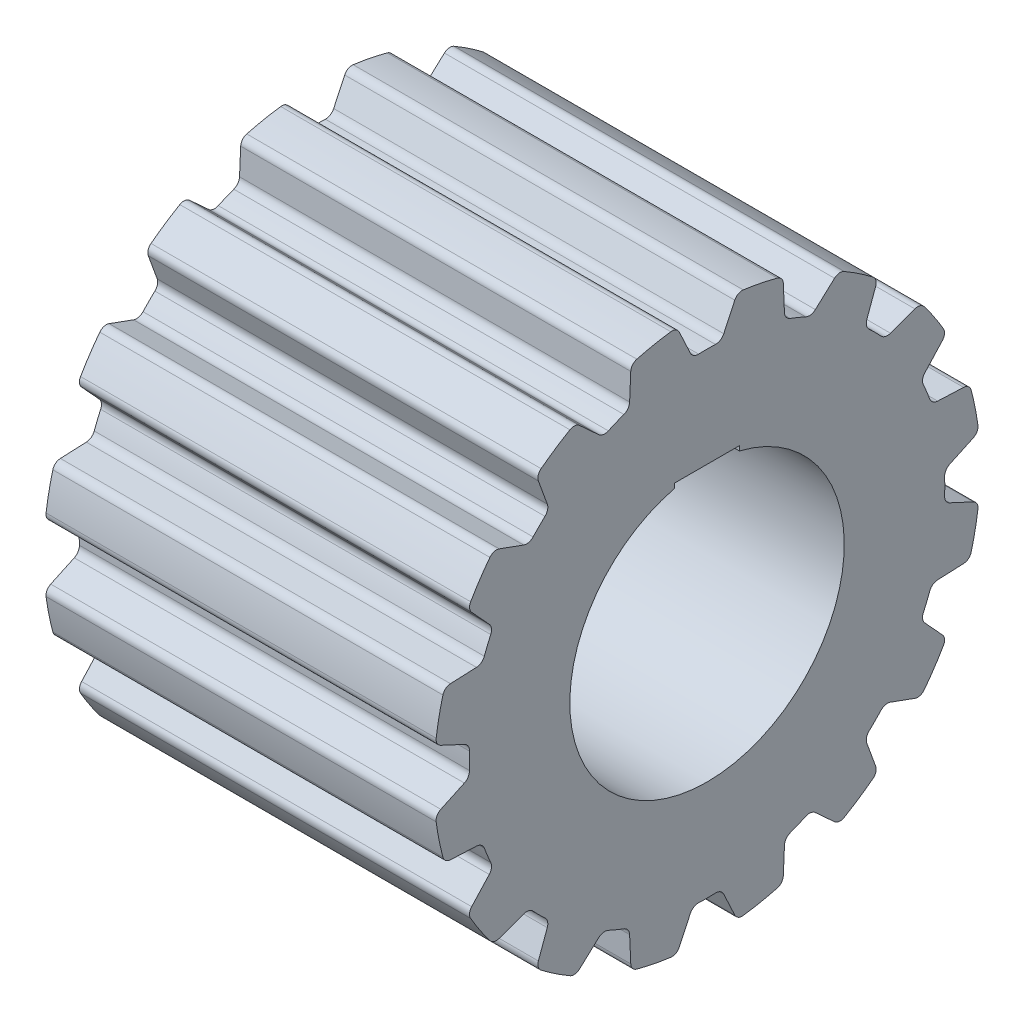
SolidWorks part; units mm, degrees
ref_plane "前视基准面" through (0, 0, 0) normal (0, 0, 1) x (1, 0, 0)
ref_plane "上视基准面" through (0, 0, 0) normal (0, 1, 0) x (1, 0, 0)
ref_plane "右视基准面" through (0, 0, 0) normal (1, 0, 0) x (0, 0, -1)
sketch "草图1" plane through (0, 0, 0) normal (0, 0, 1) x (1, 0, 0)
  line L0 (0, 0) -> (64.8368, 0) construction
  line L1 (0, 5) -> (0, 12.681)
  line L2 (0, 12.681) -> (38.1, 12.681)
  line L3 (38.1, 12.681) -> (38.1, 6.3664)
  line L4 (38.1, 6.3664) -> (6.65, 6.3664)
  line L5 (6.65, 6.3664) -> (6.65, 5)
  line L6 (6.65, 5) -> (0, 5)
  dimension "L" = 6.65
  dimension "B" = 38.1
  dimension "d" = 10
  dimension "d1" = 12.7328
  dimension "da" = 25.362
revolve "旋转1" add sketch "草图1" angle 360 about L0
chamfer "倒角1" distance 1 angle 45 2 edges at (6.65, 0, 5) (0, 0, 5)
sketch "草图4" plane through (0, 0, 0) normal (-1, 0, 0) x (0, 0, 1)
  line L1 (-1.5, 4.7697) -> (1.5, 4.7697)
  line L2 (-1.5, 4.7697) -> (-1.5, 6.4)
  line L3 (-1.5, 6.4) -> (1.5, 6.4)
  line L4 (1.5, 4.7697) -> (1.5, 6.4)
  circle A0 centre (0, 0) radius 5 construction
  point P6 (0.1, 6.4)
  dimension "键槽高度" = 6.4
  dimension "键槽宽度" = 3
  dimension "t1" = 1.4
extrude "切除-拉伸1" cut sketch "草图4" against normal through all
sketch "草图6" plane through (0, 0, 0) normal (1, 0, 0) x (0, 0, -1)
  line L0 (0, 0) -> (0, 16.0158) construction
  line L1 (1.2857, 12.3531) -> (0.7763, 11.2606)
  line L2 (2.0563, 12.5132) -> (2.6718, 13.8331)
  line L3 (-2.0563, 12.5132) -> (-2.6718, 13.8331)
  line L4 (-1.2857, 12.3531) -> (-0.7763, 11.2606)
  circle A0 centre (0, 0) radius 12.681 construction
  arc A1 (0.3902, 11.0241) -> (-0.3902, 11.0241) centre (0, 0) ccw
  arc A2 (1.6805, 12.5692) -> (2.0563, 12.5132) centre (0, 0) cw
  arc A3 (0.7763, 11.2606) -> (0.3902, 11.0241) centre (0.4047, 11.4338) cw
  arc A4 (1.2857, 12.3531) -> (1.6805, 12.5692) centre (1.6301, 12.1925) cw
  arc A5 (2.6718, 13.8331) -> (-2.6718, 13.8331) centre (0, 0) ccw
  arc A6 (-1.6805, 12.5692) -> (-2.0563, 12.5132) centre (0, 0) ccw
  arc A7 (-1.2857, 12.3531) -> (-1.6805, 12.5692) centre (-1.6301, 12.1925) ccw
  arc A8 (-0.7763, 11.2606) -> (-0.3902, 11.0241) centre (-0.4047, 11.4338) ccw
  point P8 (0, 14.3658)
  point P14 (1.4024, 12.6032)
  point P16 (0.66, 11.0112)
  dimension "D1" = 11.031
  dimension "ra" = 0.38
  dimension "rf" = 0.41
  dimension "D3" = 1.4563
  dimension "D4" = 0.38
  dimension "bw" = 1.32
  dimension "angle" = 50
  dimension "hg" = 1.65
extrude "切除-拉伸2" cut sketch "草图6" along normal up to next
ref_axis "基准轴1" through (-1.4, 0, 0) along (1, 0, 0)
pattern_circular "阵列(圆周)3" count 16 over 360 about axis through (-1.4, 0, 0) along (1, 0, 0) of "切除-拉伸2"
sketch "草图7" plane through (0, 0, 0) normal (-1, 0, 0) x (0, 0, 1)
  circle A0 centre (0, 0) radius 23.3584
extrude "切除-拉伸3" cut sketch "草图7" against normal blind 20
equation "\"键槽高度@草图4\" = \"d@草图1\" / 2  + \"t1@草图4\""
equation "\"D4@草图6\" = \"ra@草图6\""
equation "\"D1@草图6\" = \"da@草图1\" / 2 - \"hg@草图6\" "
